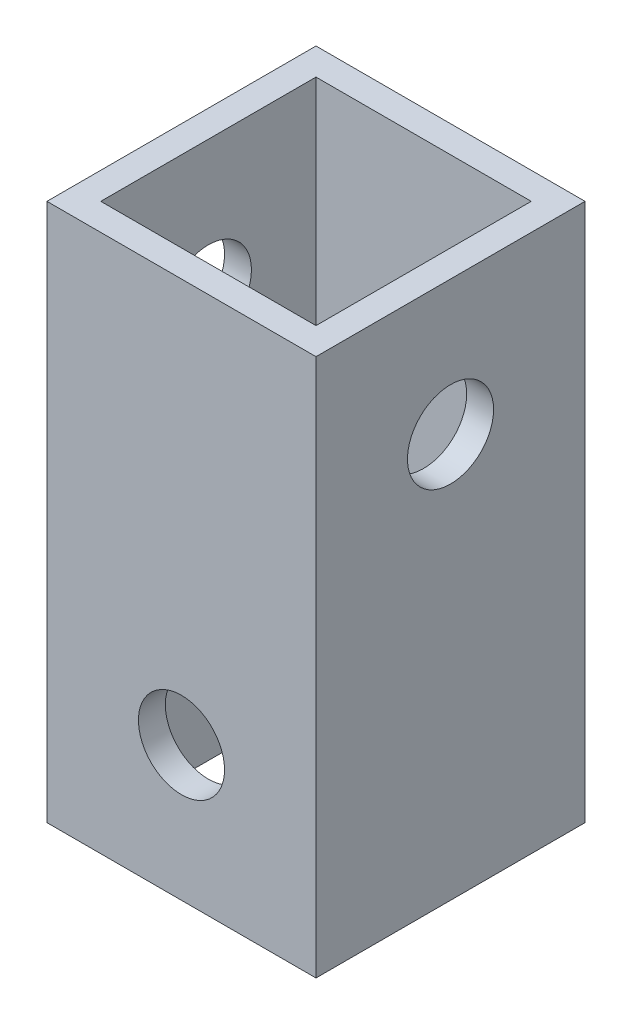
SolidWorks part; units mm, degrees
material "5052-H34"
ref_plane "正面" through (0, 0, 0) normal (0, 0, 1) x (1, 0, 0)
ref_plane "平面" through (0, 0, 0) normal (0, 1, 0) x (1, 0, 0)
ref_plane "右側面" through (0, 0, 0) normal (1, 0, 0) x (0, 0, -1)
sketch "ｽｹｯﾁ1" plane through (0, 0, 0) normal (0, 1, 0) x (1, 0, 0)
  line L1 (-5, 5) -> (5, 5)
  line L2 (-5, 5) -> (-5, -5)
  line L3 (-5, -5) -> (5, -5)
  line L4 (5, 5) -> (5, -5)
  line L5 (-5, 5) -> (5, -5) construction
  line L6 (-5, -5) -> (5, 5) construction
  point P0 (0, 0)
  dimension "D1" = 10
  dimension "D2" = 10
extrude "押し出し-薄板1" add sketch "ｽｹｯﾁ1" along normal blind 20 thin thin type one direction reverse wall 1
sketch "ｽｹｯﾁ2" plane through (0, 0, 5) normal (0, 0, 1) x (1, 0, 0)
  line L0 (0, 0) -> (0, 5) construction
  circle A0 centre (0, 5) radius 1.6
  dimension "D2" = 3.2
  dimension "D1" = 5
extrude "ｶｯﾄ - 押し出し1" cut sketch "ｽｹｯﾁ2" against normal through all
sketch "ｽｹｯﾁ3" plane through (5, 0, 0) normal (1, 0, 0) x (0, 0, -1)
  line L0 (0, 20) -> (0, 15) construction
  line L1 (-5, 20) -> (5, 20) construction
  circle A0 centre (0, 15) radius 1.6
  dimension "D1" = 3.2
  dimension "D2" = 5
extrude "ｶｯﾄ - 押し出し2" cut sketch "ｽｹｯﾁ3" against normal through all
